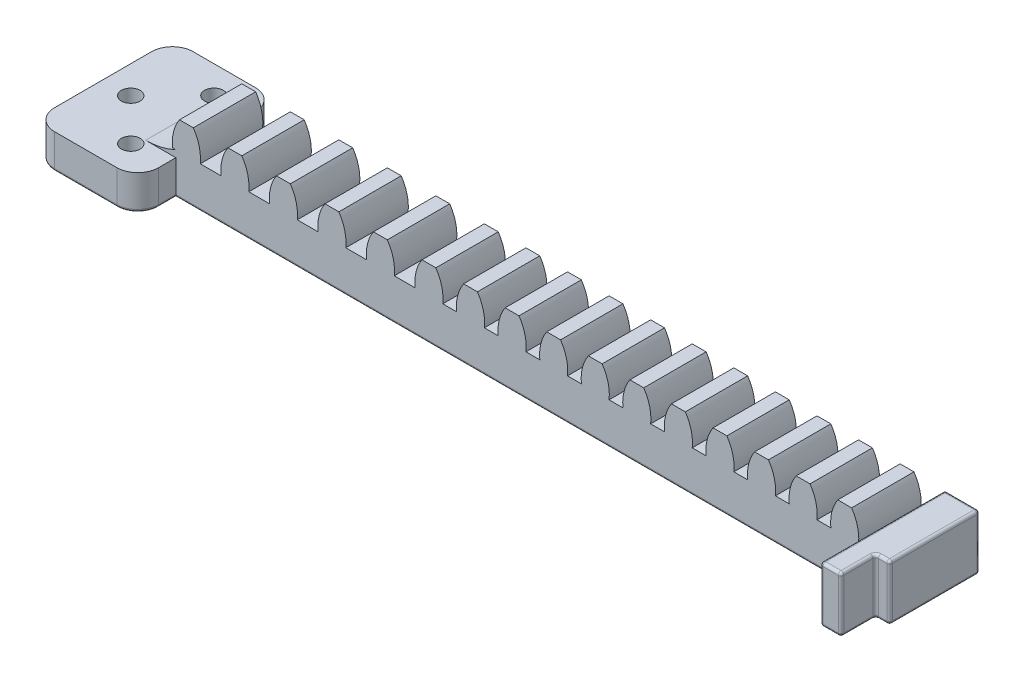
SolidWorks part; units mm, degrees
ref_plane "Front Plane" through (0, 0, 0) normal (0, 0, 1) x (1, 0, 0)
ref_plane "Top Plane" through (0, 0, 0) normal (0, 1, 0) x (1, 0, 0)
ref_plane "Right Plane" through (0, 0, 0) normal (1, 0, 0) x (0, 0, -1)
sketch "Sketch1" plane through (0, 0, 0) normal (0, 0, 1) x (1, 0, 0)
  line L0 (-24.1927, -27.8293) -> (-24.1927, -33.8096) construction
  line L1 (-60.7191, -43.8293) -> (39.2809, -43.8293)
  line L2 (-60.7191, -43.8293) -> (-60.7191, -37.8293)
  line L3 (-60.7191, -37.8293) -> (39.2809, -37.8293)
  line L4 (39.2809, -43.8293) -> (39.2809, -37.8293)
  line L5 (-25.1927, -33.8293) -> (-23.1927, -33.8293)
  arc A3 (-26.1927, -37.8293) -> (-25.1927, -33.8293) centre (-20.2262, -37.1959) cw
  arc A5 (-22.1927, -37.8293) -> (-23.1927, -33.8293) centre (-28.1591, -37.1959) ccw
  arc M24 (-26.1927, -33.4862) -> (-25.1927, -37.7792) centre (-16.1929, -33.4198) ccw
  arc M25 (-25.1927, -37.7792) -> (-23.1927, -37.7792) centre (-24.1927, -27.8293) ccw
  arc M26 (-23.1927, -37.7792) -> (-22.1927, -33.4862) centre (-32.1924, -33.4198) ccw
  dimension "D4" = 6
  dimension "D1" = 100
  dimension "D2" = 6
  dimension "D5" = 1
  dimension "D6" = 2
  dimension "D7" = 4
extrude "Boss-Extrude1" add sketch "Sketch1" against normal up to surface (9 mm away) contours L1 L4 L3 L2 region at (-10.7191, -40.8293, 0)
extrude "Boss-Extrude2" add sketch "Sketch1<3>" against normal up to surface (9 mm away) contours L3 A5 L5 A3 | A3 L3 M25 M24 | L3 A5 M26 M25 region at (-25.8372, -37.039, 0) region at (-22.5481, -37.039, 0) region at (-24.1927, -35.7872, 0) up to face at (-10.7191, -40.8293, -9)
sketch "Sketch1<3>" plane through (0, 0, 0) normal (0, 0, 1) x (1, 0, 0) same geometry as "Sketch1"
pattern_linear "LPattern1" count 6 spacing 7 along (-1, 0, 0) count 11 spacing 6 along (1, 0, 0) of "Boss-Extrude2" pattern seed only yes
sketch "Sketch2" plane through (0, -43.8293, 0) normal (0, -1, 0) x (1, 0, 0)
  line L0 (-60.7191, -9) -> (-60.7191, 0) construction
  line L1 (-60.7191, -14.5) -> (-75.7191, -14.5)
  line L2 (-60.7191, -14.5) -> (-60.7191, 5.5)
  line L3 (-60.7191, 5.5) -> (-75.7191, 5.5)
  line L4 (-75.7191, -14.5) -> (-75.7191, 5.5)
  line L5 (39.2809, -9) -> (39.2809, 0) construction
  point P8 (39.2809, -4.5)
  point P9 (-60.7191, -4.5)
  dimension "D1" = 15
  dimension "D2" = 20
extrude "Boss-Extrude3" add sketch "Sketch2" against normal blind 5
fillet "Fillet1" radius 10 1 edges at (-60.7191, -38.8293, -4.5)
fillet "Fillet2" radius 3 4 edges at (-60.7191, -41.3293, -14.5) (-75.7191, -41.3293, -14.5) (-75.7191, -41.3293, 5.5) (-60.7191, -41.3293, 5.5)
sketch "Sketch3" plane through (39.2809, 0, 0) normal (1, 0, 0) x (0, 0, -1)
  line L4 (11, -35.8293) -> (-2, -35.8293)
  line L12 (-2, -43.8293) -> (11, -43.8293)
  line L13 (11.5, -43.8293) -> (9, -43.8293) construction
  line L14 (0, -43.8293) -> (-2.5, -43.8293) construction
  line L15 (11, -35.8293) -> (-2, -35.8293)
  line L16 (11, -45.8293) -> (11, -35.8293)
  line L18 (-2, -35.8293) -> (-2, -45.8293)
  line L19 (-2, -45.8293) -> (11, -45.8293)
  line L20 (11, -43.8293) -> (11, -35.8293)
  line L22 (-2, -35.8293) -> (-2, -43.8293)
  dimension "D1" = 2
extrude "Boss-Extrude4" add sketch "Sketch3" along normal blind 5
sketch "Sketch4" plane through (0, 0, 2) normal (0, 0, 1) x (1, 0, 0)
  line L1 (39.2809, -43.8293) -> (42.2809, -43.8293)
  line L2 (39.2809, -43.8293) -> (39.2809, -35.8293)
  line L3 (39.2809, -35.8293) -> (42.2809, -35.8293)
  line L4 (42.2809, -43.8293) -> (42.2809, -35.8293)
  dimension "D1" = 3
  dimension "D2" = 8
extrude "Boss-Extrude5" add sketch "Sketch4" along normal blind 5
fillet "Fillet3" radius 0.4 29 edges at (-74.8404, -43.8293, -13.6213) (-75.7191, -43.8293, -4.5) (-74.8404, -43.8293, 4.6213) (-68.2191, -43.8293, 5.5) (-61.5978, -43.8293, 4.6213) (-60.7191, -43.8293, 1.25) (-10.7191, -43.8293, 0) (39.2809, -43.8293, 3.5) (41.7809, -43.8293, -11) (39.2809, -43.8293, -10) (-10.7191, -43.8293, -9) (-60.7191, -43.8293, -10.25) (-61.5978, -43.8293, -13.6213) (-68.2191, -43.8293, -14.5) (40.7809, -43.8293, 7) (39.2809, -39.8293, 7) (43.2809, -43.8293, 2) (42.2809, -43.8293, 4.5) (42.2809, -39.8293, 7) (42.2809, -39.8293, 2) (44.2809, -39.8293, -11) (44.2809, -43.8293, -4.5) (44.2809, -39.8293, 2) (41.7809, -35.8293, -11) (44.2809, -35.8293, -4.5) (43.2809, -35.8293, 2) (42.2809, -35.8293, 4.5) (40.7809, -35.8293, 7) (39.2809, -35.8293, -2)
hole_wizard "Ø3.0mm Dowel Hole1" positions "3DSketch1" profile "Sketch5" hole size "Ø3.0" standard "ANSI Metric"
sketch3d "3DSketch1"
  line L5 (-72.7191, -43.4293, 5.5) -> (-63.7191, -43.4293, 5.5) construction
  point P0 (-65.7191, -43.8293, 1.5)
  point P2 (-65.7191, -43.8293, -10.5)
  point P4 (-71.7191, -43.8293, -4.492)
  dimension "D1" = 10
  dimension "D2" = 4
  dimension "D3" = 4
  dimension "D4" = 10
  dimension "D5" = 10
  dimension "D6" = 4
sketch "Sketch5" plane through (-65.7191, -43.8293, 1.5) normal (1, 0, 0) x (0, 0, -1)
  line L0 (0, 0) -> (0, 7.8112)
  line L1 (0, 7.8112) -> (1.35, 7)
  line L2 (1.35, 7) -> (1.35, 0)
  line L5 (1.35, 0) -> (0, 0)
  line L10 (0, 7.8112) -> (-1.35, 7) construction
  line L11 (0, -6.35) -> (0, 107.95) construction
  dimension "Hole Dia." = 2.7
  dimension "Hole Depth" = 7
  dimension "Drill Angle" = 118
